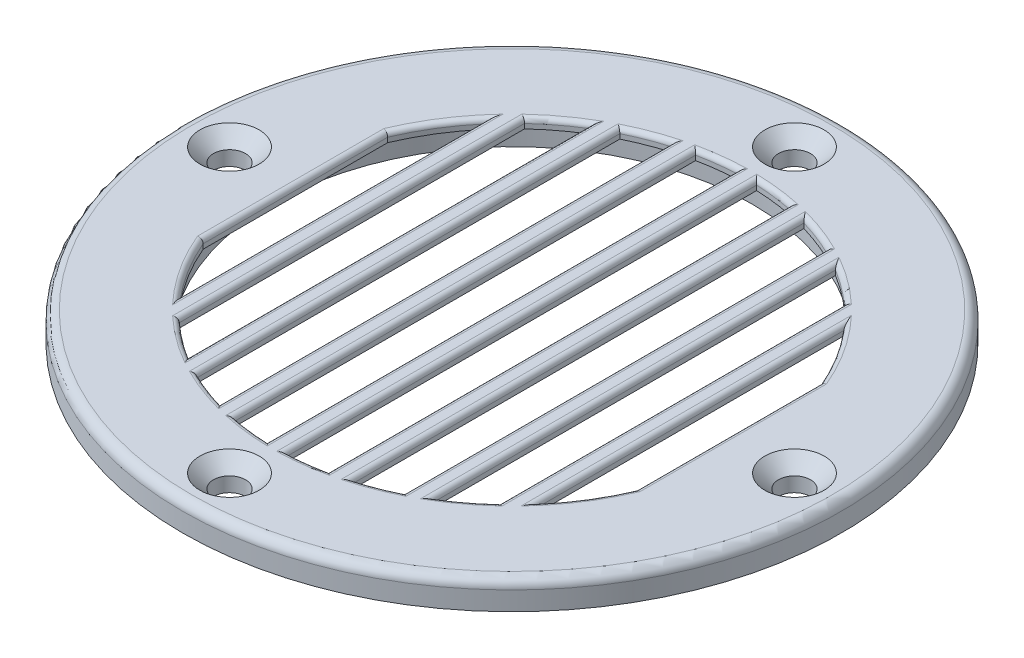
SolidWorks part; units mm, degrees
ref_plane "Front Plane" through (0, 0, 0) normal (0, 0, 1) x (1, 0, 0)
ref_plane "Top Plane" through (0, 0, 0) normal (0, 1, 0) x (1, 0, 0)
ref_plane "Right Plane" through (0, 0, 0) normal (1, 0, 0) x (0, 0, -1)
sketch "Sketch1" plane through (0, 0, 0) normal (0, 1, 0) x (1, 0, 0)
  line L0 (0, -25) -> (0, 25) construction
  line L1 (6, -24.2693) -> (6, 24.2693) construction
  line L2 (12, -21.9317) -> (12, 21.9317) construction
  line L3 (18, -17.3494) -> (18, 17.3494) construction
  line L4 (24, -7) -> (24, 7) construction
  line L5 (-6, -24.2693) -> (-6, 24.2693) construction
  line L6 (-12, -21.9317) -> (-12, 21.9317) construction
  line L7 (-18, -17.3494) -> (-18, 17.3494) construction
  line L8 (-24, -7) -> (-24, 7) construction
  line L9 (1, -24.98) -> (1, 24.98)
  line L10 (7, -24) -> (7, 24)
  line L11 (13, -21.3542) -> (13, 21.3542)
  line L12 (19, -16.2481) -> (19, 16.2481)
  line L13 (25, -25) -> (25, -24.4949)
  line L14 (-5, -24.4949) -> (-5, 24.4949)
  line L15 (-11, -22.4499) -> (-11, 22.4499)
  line L16 (-17, -18.3303) -> (-17, 18.3303)
  line L17 (-23, -9.798) -> (-23, 9.798)
  line L18 (-1, -24.98) -> (-1, 24.98)
  line L19 (-7, -24) -> (-7, 24)
  line L20 (-13, -21.3542) -> (-13, 21.3542)
  line L21 (-19, -16.2481) -> (-19, 16.2481)
  line L22 (-25, -25) -> (-25, -24.4949)
  line L23 (5, -24.4949) -> (5, 24.4949)
  line L24 (11, -22.4499) -> (11, 22.4499)
  line L25 (17, -18.3303) -> (17, 18.3303)
  line L26 (23, -9.798) -> (23, 9.798)
  line L27 (-25, 24.4949) -> (-25, 25)
  line L28 (-25, -25) -> (-25, 25) construction
  line L29 (-24, -25) -> (-24, 25) construction
  line L30 (-23, -25) -> (-23, 25) construction
  line L31 (-19, -25) -> (-19, 25) construction
  line L32 (-18, -25) -> (-18, 25) construction
  line L33 (-17, -25) -> (-17, 25) construction
  line L34 (-13, -25) -> (-13, 25) construction
  line L35 (-12, -25) -> (-12, 25) construction
  line L36 (-11, -25) -> (-11, 25) construction
  line L37 (-7, -25) -> (-7, 25) construction
  line L38 (-6, -25) -> (-6, 25) construction
  line L39 (-5, -25) -> (-5, 25) construction
  line L40 (-1, -25) -> (-1, 25) construction
  line L41 (1, -25) -> (1, 25) construction
  line L42 (5, -25) -> (5, 25) construction
  line L43 (6, -25) -> (6, 25) construction
  line L44 (7, -25) -> (7, 25) construction
  line L45 (11, -25) -> (11, 25) construction
  line L46 (12, -25) -> (12, 25) construction
  line L47 (13, -25) -> (13, 25) construction
  line L48 (17, -25) -> (17, 25) construction
  line L49 (18, -25) -> (18, 25) construction
  line L50 (19, -25) -> (19, 25) construction
  line L51 (23, -25) -> (23, 25) construction
  line L52 (24, -25) -> (24, 25) construction
  line L53 (25, 24.4949) -> (25, 25)
  line L54 (25, -25) -> (25, 25) construction
  circle A0 centre (0, 0) radius 35
  arc A1 (-19, 16.2481) -> (-23, 9.798) centre (0, 0) ccw
  arc A2 (-23, -9.798) -> (-19, -16.2481) centre (0, 0) ccw
  arc A3 (-13, 21.3542) -> (-17, 18.3303) centre (0, 0) ccw
  arc A4 (-7, 24) -> (-11, 22.4499) centre (0, 0) ccw
  arc A5 (-1, 24.98) -> (-5, 24.4949) centre (0, 0) ccw
  arc A6 (5, 24.4949) -> (1, 24.98) centre (0, 0) ccw
  arc A7 (11, 22.4499) -> (7, 24) centre (0, 0) ccw
  arc A8 (17, 18.3303) -> (13, 21.3542) centre (0, 0) ccw
  arc A9 (23, 9.798) -> (19, 16.2481) centre (0, 0) ccw
  arc A10 (19, -16.2481) -> (23, -9.798) centre (0, 0) ccw
  arc A11 (13, -21.3542) -> (17, -18.3303) centre (0, 0) ccw
  arc A12 (7, -24) -> (11, -22.4499) centre (0, 0) ccw
  arc A13 (1, -24.98) -> (5, -24.4949) centre (0, 0) ccw
  arc A14 (-5, -24.4949) -> (-1, -24.98) centre (0, 0) ccw
  arc A15 (-11, -22.4499) -> (-7, -24) centre (0, 0) ccw
  arc A16 (-17, -18.3303) -> (-13, -21.3542) centre (0, 0) ccw
  point P7 (0, 0)
  dimension "D1" = 70
  dimension "D2" = 50
  dimension "D3" = 6
  dimension "D4" = 6
  dimension "D5" = 6
  dimension "D6" = 6
  dimension "D7" = 6
  dimension "D8" = 6
  dimension "D9" = 6
  dimension "D10" = 6
  dimension "D11" = 1
  dimension "D12" = 1
extrude "Boss-Extrude1" add sketch "Sketch1" along normal blind 3 contours A0 A16 L16 A3 L20 A15 L15 A4 L19 A14 L14 A5 L18 A13 L9 A6 L23 A12 L10 A7 L24 A11 L11 A8 L25 A10 L12 A9 L26 A2 L17 A1 L21 region at (0, 0, 0)
sketch "Sketch2" plane through (0, 3, 0) normal (0, 1, 0) x (1, 0, 0)
  line L0 (-35, 0) -> (35, 0) construction
  circle A0 centre (0, 0) radius 35 construction
  point P0 (30, 0)
  point P7 (0, 0)
  point P12 (0, -30)
  point P13 (-30, 0)
  point P14 (0, 30)
  point P15 (0, 0)
  dimension "D1" = 5
  dimension "D3" = 90
  dimension "D4" = 30
  dimension "D2" = 4
hole_wizard "CSK for M3 Flat Head Machine Screw1" positions "Sketch3" profile "Sketch4" countersink size "M3" standard "ANSI Metric" end condition through all
sketch "Sketch3" plane through (0, 3, 0) normal (0, 1, 0) x (1, 0, 0)
  point P0 (30, 0)
  point P3 (0, -30)
  point P6 (-30, 0)
  point P9 (0, 30)
sketch "Sketch4" plane through (30, 3, 0) normal (1, 0, 0) x (0, 0, 1)
  line L0 (0, 0) -> (0, 3)
  line L1 (0, 3) -> (1.7, 3)
  line L2 (1.7, 3) -> (1.7, 1.45)
  line L3 (1.7, 1.45) -> (3.15, 0)
  line L5 (3.15, 0) -> (0, 0)
  line L6 (-1.7, 1.45) -> (-3.15, 0) construction
  line L11 (0, -6.35) -> (0, 107.95) construction
  dimension "Thru Hole Dia." = 3.4
  dimension "Thru Hole Depth" = 3
  dimension "Near C'Sink Dia." = 6.3
  dimension "Near C'Sink Angle" = 90
fillet "Fillet1" radius 1 1 edges at (0, 3, 35)
fillet "Fillet3" radius 0.5 32 edges at (21.2462, 3, -13.1757) (15.076, 3, -19.9428) (9.0333, 3, -23.3109) (3.0098, 3, -24.8182) (-3.0098, 3, -24.8182) (-9.0333, 3, -23.3109) (-15.076, 3, -19.9428) (-21.2462, 3, -13.1757) (-21.2462, 3, 13.1757) (-15.076, 3, 19.9428) (-9.0333, 3, 23.3109) (-3.0098, 3, 24.8182) (3.0098, 3, 24.8182) (9.0333, 3, 23.3109) (15.076, 3, 19.9428) (21.2462, 3, 13.1757) (23, 3, 0) (17, 3, 0) (11, 3, 0) (5, 3, 0) (-1, 3, 0) (-7, 3, 0) (-13, 3, 0) (-19, 3, 0) (19, 3, 0) (13, 3, 0) (7, 3, 0) (1, 3, 0) (-5, 3, 0) (-11, 3, 0) (-17, 3, 0) (-23, 3, 0)
sketch "Sketch5" plane through (0, 0, 0) normal (0, -1, 0) x (1, 0, 0)
  circle A0 centre (0, 0) radius 25.5
  dimension "D1" = 51
extrude "Cut-Extrude1" cut sketch "Sketch5" against normal blind 2
